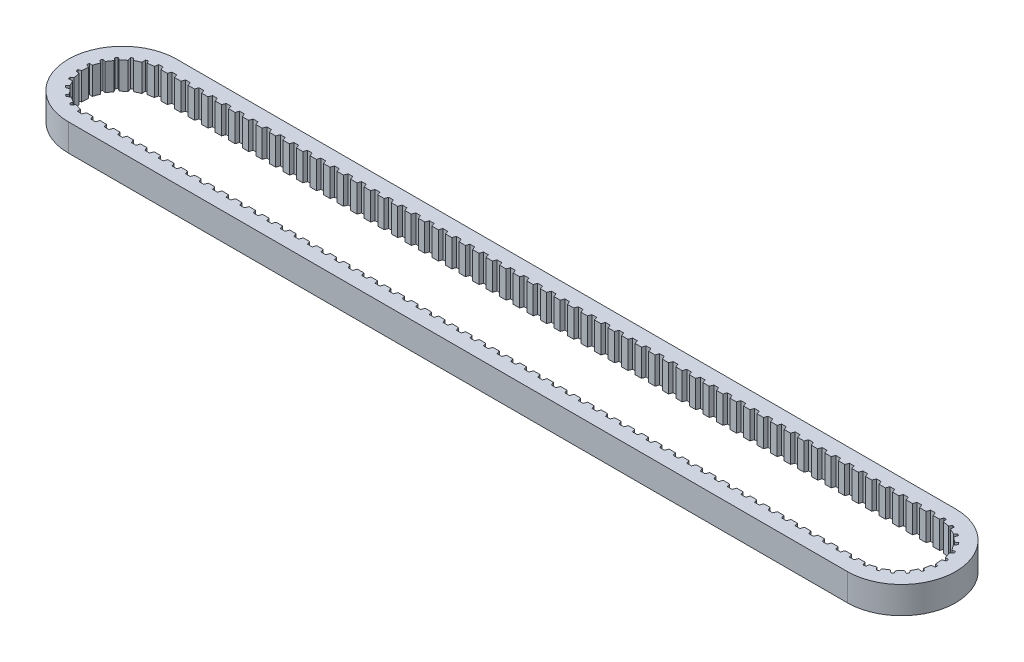
SolidWorks part; units mm, degrees
ref_plane "Front Plane" through (0, 0, 0) normal (0, 0, 1) x (1, 0, 0)
ref_plane "Top Plane" through (0, 0, 0) normal (0, 1, 0) x (1, 0, 0)
ref_plane "Right Plane" through (0, 0, 0) normal (1, 0, 0) x (0, 0, -1)
sketch "Sketch1" plane through (0, 0, 0) normal (0, 1, 0) x (1, 0, 0)
  line L0 (-115, -8) -> (0, -8)
  line L1 (-115, 8) -> (0, 8)
  circle A0 centre (0, 0) radius 8
  circle A1 centre (-115, 0) radius 8
  dimension "D1" = 16
  dimension "D2" = 16
  dimension "D3" = 115
extrude "Boss-Extrude1" add sketch "Sketch1" along normal blind 4 contours A1 L0 A0 L1 | A1 | A0 region at (-57.5, 0, 0) region at (-115, 0, 0) region at (0, 0, 0)
shell "Shell1" thickness 2 removed face at (-57.5, 0, 0) removed face at (-57.5, 4, 0)
sketch "Sketch2" plane through (0, 0, 0) normal (0, -1, 0) x (1, 0, 0)
  line L0 (-115, 6) -> (-114.818, 5.5)
  line L1 (-114.818, 5.5) -> (-113.882, 5.5)
  line L2 (-113.882, 5.5) -> (-113.7, 6)
  line L3 (-115, 6) -> (0, 6) construction
  line L4 (-113.7, 6) -> (-115, 6)
  dimension "D1" = 1.3
  dimension "D2" = 70
  dimension "D3" = 70
  dimension "D4" = 0.5
extrude "Boss-Extrude2" add sketch "Sketch2" against normal blind 4
pattern_linear "LPattern1" count 58 spacing 2 along (1, 0, 0) of "Boss-Extrude2"
ref_plane "Plane1" through (0, 0, 0) normal (0, 0, -1) x (-1, 0, 0)
mirror "Mirror1" about plane through (0, 0, 0) normal (0, 0, -1) of "LPattern1"
sketch "Sketch4" plane through (0, 0, 0) normal (0, -1, 0) x (1, 0, 0)
  line L0 (-115.6988, 5.9592) -> (-115.7251, 5.5099)
  line L1 (-115.7251, 5.5099) -> (-116.6256, 5.2405)
  line L2 (-116.6256, 5.2405) -> (-116.9488, 5.6747)
  arc A0 (-115, 6) -> (-115, -6) centre (-115, 0) ccw construction
  arc A1 (-115.6988, 5.9592) -> (-116.9488, 5.6747) centre (-115, 0) ccw
  point P10 (-116.3314, 5.8504)
  point P11 (0, 0)
  point P13 (-116.919, 5.6718)
  dimension "D1" = 110
  dimension "D2" = 110
  dimension "D3" = 0.94
  dimension "D4" = 0.5
  dimension "D5" = 0.7
  dimension "D6" = 0.45
extrude "Boss-Extrude3" add sketch "Sketch4" against normal blind 4
pattern_circular "CirPattern1" count 11 every 15.5 about axis through (-115, 0, 0) along (0, 1, 0) of "Boss-Extrude3" reverse direction yes
ref_plane "Plane2" through (-57.5, 0, -8) normal (-1, 0, 0) x (0, 0, 1)
mirror "Mirror2" about plane through (-57.5, 0, -8) normal (-1, 0, 0) of "CirPattern1"
